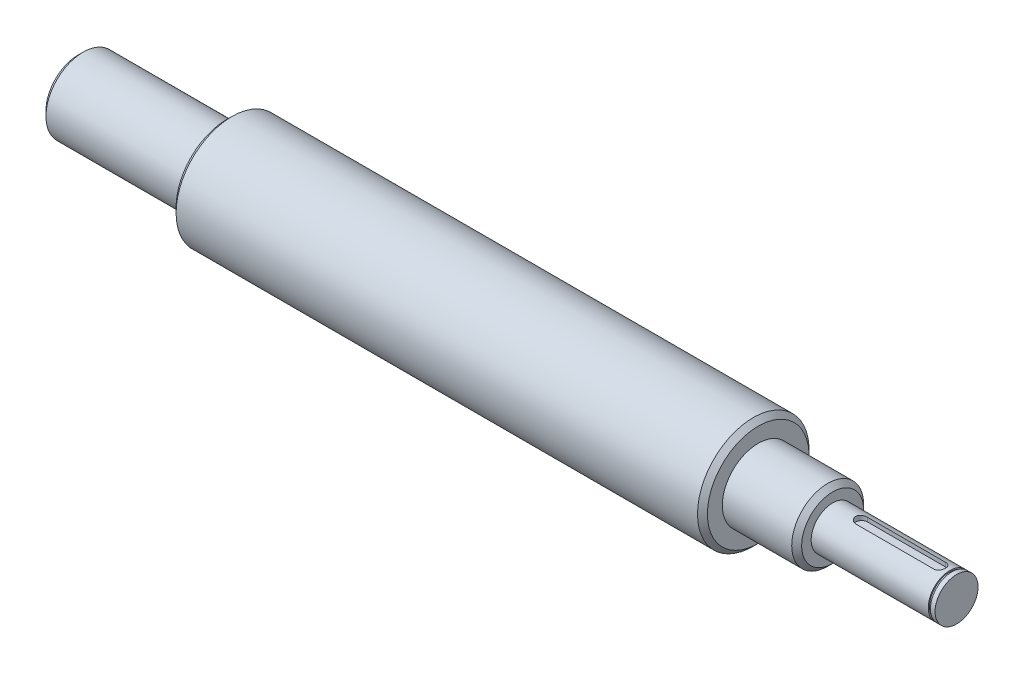
SolidWorks part; units mm, degrees
ref_plane "Front Plane" through (0, 0, 0) normal (0, 0, 1) x (1, 0, 0)
ref_plane "Top Plane" through (0, 0, 0) normal (0, 1, 0) x (1, 0, 0)
ref_plane "Right Plane" through (0, 0, 0) normal (1, 0, 0) x (0, 0, -1)
sketch "Sketch1" plane through (0, 0, 0) normal (0, 0, 1) x (1, 0, 0)
  line L0 (-1910.9611, 0) -> (93637.0942, 0) construction
  line L1 (-225, 0) -> (225, 0)
  line L2 (-225, 0) -> (-225, 19.05)
  line L3 (-225, 19.05) -> (-148.8, 19.05)
  line L4 (-148.8, 19.05) -> (-148.8, 28.575)
  line L5 (-148.8, 28.575) -> (123.4, 28.575)
  line L6 (123.4, 28.575) -> (123.4, 18.415)
  line L7 (123.4, 18.415) -> (161.5, 18.415)
  line L8 (161.5, 18.415) -> (161.5, 11)
  line L9 (161.5, 11) -> (225, 11)
  line L10 (225, 11) -> (225, 0)
  point P5 (0, 0)
  dimension "D1" = 450
  dimension "D2" = 38.1
  dimension "D3" = 76.2
  dimension "D4" = 57.15
  dimension "D5" = 38.1
  dimension "D6" = 36.83
  dimension "D7" = 22
  dimension "D8" = 63.5
revolve "Revolve1" add sketch "Sketch1" angle 360 about L0
chamfer "Chamfer1" distance 2.54 angle 45 2 edges at (161.5, 0, 18.415) (123.4, 0, 28.575)
chamfer "Chamfer2" distance 2.54 angle 45 2 edges at (-148.8, 0, 28.575) (-225, 0, 19.05)
fillet "Fillet1" radius 2.54 1 edges at (-148.8, 0, 19.05)
ref_plane "Plane2" through (0, 11, 0) normal (0, 1, 0) x (1, 0, 0)
sketch "Sketch3" plane through (0, 11, 0) normal (0, 1, 0) x (1, 0, 0)
  line L0 (166.375, 0) -> (176.375, 0) construction
  line L1 (166.375, -11) -> (166.375, 11) construction
  line L2 (176.375, 0) -> (216.375, 0) construction
  line L3 (176.375, 3) -> (216.375, 3)
  line L4 (176.375, -3) -> (216.375, -3)
  arc A0 (176.375, 3) -> (176.375, -3) centre (176.375, 0) ccw
  arc A1 (216.375, -3) -> (216.375, 3) centre (216.375, 0) ccw
  point P5 (196.375, 0)
  dimension "D1" = 10
  dimension "D2" = 40
  dimension "D3" = 6
extrude "Cut-Extrude2" cut sketch "Sketch3" against normal blind 2.5
ref_plane "Plane3" through (221.4977, 0, 0) normal (1, 0, 0) x (0, 0, -1)
sketch "Sketch7" plane through (221.4977, 0, 0) normal (1, 0, 0) x (0, 0, -1)
  circle A0 centre (0, 0) radius 10.35
  circle A1 centre (0, 0) radius 11
  dimension "D1" = 20.7
extrude "Cut-Extrude3" cut sketch "Sketch7" along normal blind 1.1
equation "\"D5@Sketch1\"=\"D3@Sketch1\"/2"
